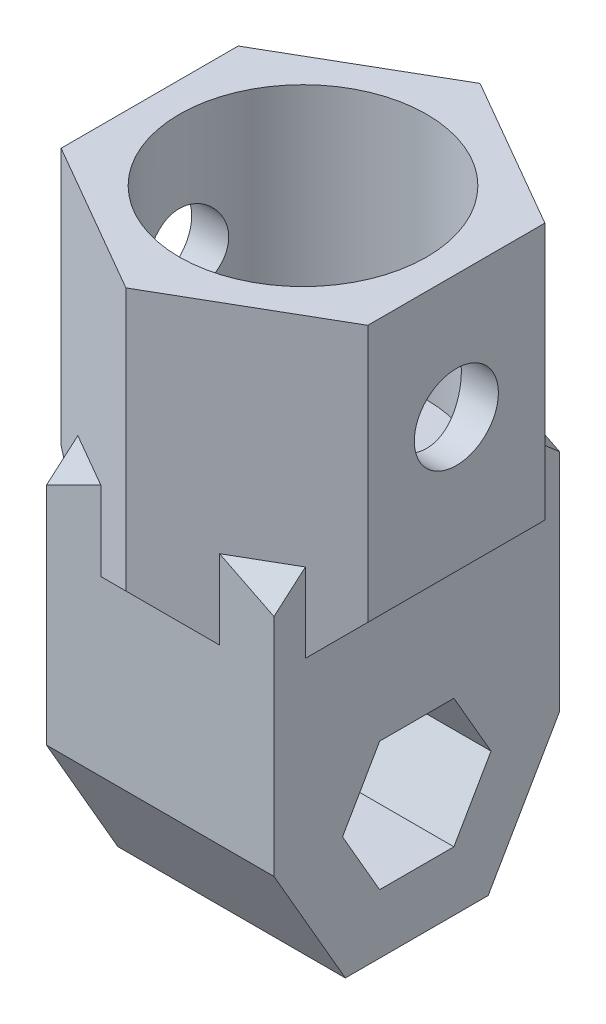
SolidWorks part; units mm, degrees
ref_plane "Alzado" through (0, 0, 0) normal (0, 0, 1) x (1, 0, 0)
ref_plane "Planta" through (0, 0, 0) normal (0, 1, 0) x (1, 0, 0)
ref_plane "Vista lateral" through (0, 0, 0) normal (1, 0, 0) x (0, 0, -1)
sketch "Croquis1" plane through (0, 0, 0) normal (1, 0, 0) x (0, 0, -1)
  line L0 (0, 0) -> (3.0022, 0) construction
  line L1 (3.0022, 0) -> (1.5011, 2.6)
  line L2 (1.5011, 2.6) -> (-1.5011, 2.6)
  line L3 (-1.5011, 2.6) -> (-3.0022, 0)
  line L4 (-3.0022, 0) -> (-1.5011, -2.6)
  line L5 (-1.5011, -2.6) -> (1.5011, -2.6)
  line L6 (1.5011, -2.6) -> (3.0022, 0)
  line L7 (2.8868, 5) -> (-2.8868, 5)
  line L8 (-2.8868, 5) -> (-5.7735, 0)
  line L9 (-5.7735, 0) -> (-2.8868, -5)
  line L10 (-2.8868, -5) -> (2.8868, -5)
  line L11 (2.8868, -5) -> (5.7735, 0)
  line L12 (5.7735, 0) -> (2.8868, 5)
  circle A0 centre (0, 0) radius 2.6 construction
  point P1 (0, -2.6)
  dimension "D1" = 5.2
  dimension "D2" = 2.4
extrude "Saliente-Extruir1" add sketch "Croquis1" along normal blind 4.6 and the other way blind 4.6
ref_plane "Plano1" through (0, 5, 0) normal (0, 1, 0) x (1, 0, 0)
sketch "Croquis2" plane through (0, 5, 0) normal (0, 1, 0) x (1, 0, 0)
  line L0 (0, 0) -> (0, 7.1591) construction
  line L1 (0, 7.1591) -> (-6.2, 3.5796)
  line L2 (-6.2, 3.5796) -> (-6.2, -3.5796)
  line L3 (-6.2, -3.5796) -> (0, -7.1591)
  line L4 (0, -7.1591) -> (6.2, -3.5796)
  line L5 (6.2, -3.5796) -> (6.2, 3.5796)
  line L6 (6.2, 3.5796) -> (0, 7.1591)
  circle A0 centre (0, 0) radius 5
  circle A1 centre (0, 0) radius 6.2 construction
  dimension "D1" = 10
  dimension "D2" = 12.4
extrude "Saliente-Extruir2" add sketch "Croquis2" along normal blind 10 from offset 4 separate body
sketch "Croquis4" plane through (0, 0, 0) normal (0, 1, 0) x (1, 0, 0)
  line L1 (-4.6, -5.7735) -> (4.6, -5.7735)
  line L2 (-4.6, -5.7735) -> (-4.6, -3.0022)
  line L3 (-4.6, -3.0022) -> (4.6, -3.0022)
  line L4 (4.6, -5.7735) -> (4.6, -3.0022)
  line L5 (4.6, 3.0022) -> (-4.6, 3.0022)
  line L6 (4.6, 3.0022) -> (4.6, 5.7735)
  line L7 (4.6, 5.7735) -> (-4.6, 5.7735)
  line L8 (-4.6, 3.0022) -> (-4.6, 5.7735)
  line L9 (-4.6, 3.0022) -> (4.6, 3.0022)
  line L10 (-4.6, 3.0022) -> (-4.6, -3.0022)
  line L11 (-4.6, -3.0022) -> (4.6, -3.0022)
  line L12 (4.6, 3.0022) -> (4.6, -3.0022)
extrude "Saliente-Extruir3" add sketch "Croquis4" along normal up to surface (9 mm away) contours L1 L4 L3 L2 | L8 L5 L6 L7 region at (0, 0, 4.3879) region at (0, 0, -4.3879) up to face at (0, 9, 0)
extrude "Saliente-Extruir4" add sketch "Croquis4<3>" along normal up to surface (9 mm away) from surface contours L12 L5 L10 L3 region at (0, 0, 0) up to face at (4.9748, 9, 0) starting at face at (0, 2.6, 0)
sketch "Croquis4<3>" plane through (0, 0, 0) normal (0, 1, 0) x (1, 0, 0) same geometry as "Croquis4"
extrude "Saliente-Extruir5" add sketch "Croquis2<2>" against normal blind 0.4 from surface contours A0 | L5 L6 L1 L2 L3 L4 A0 region at (3.0053, 5, -5.2053) region at (0, 5, 0) starting at face at (-5.2, 9, 0)
sketch "Croquis2<2>" plane through (0, 5, 0) normal (0, 1, 0) x (1, 0, 0) same geometry as "Croquis2"
chamfer "Chaflán1" distance 1.2 angle 45 4 edges at (3.5, 9, 5.1384) (-3.5, 9, 5.1384) (-3.5, 9, -5.1384) (3.5, 9, -5.1384)
chamfer "Chaflán2" distance 1.6 angle 45 4 edges at (4.6, 8.6, 0) (0, 8.6, -5.7735) (-4.6, 8.6, 0) (0, 8.6, 5.7735)
ref_plane "Plano2" through (6.2, 0, 0) normal (1, 0, 0) x (0, 0, -1)
sketch "Croquis5" plane through (6.2, 0, 0) normal (1, 0, 0) x (0, 0, -1)
  line L0 (3.5796, 19) -> (0, 19) construction
  line L1 (-3.5796, 19) -> (3.5796, 19) construction
  line L2 (0, 19) -> (0, 14) construction
  circle A0 centre (0, 14) radius 1.7
  dimension "D2" = 3.4
  dimension "D1" = 5
extrude "Cortar-Extruir1" cut sketch "Croquis5" against normal through all
